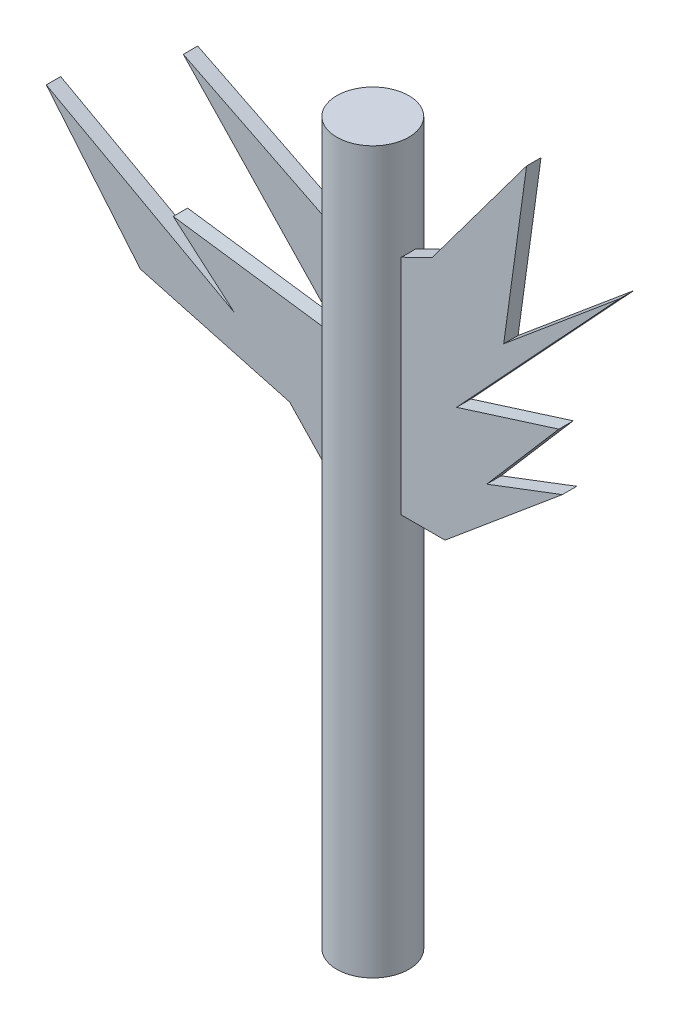
SolidWorks part; units mm, degrees
ref_plane "前视基准面" through (0, 0, 0) normal (0, 0, 1) x (1, 0, 0)
ref_plane "上视基准面" through (0, 0, 0) normal (0, 1, 0) x (1, 0, 0)
ref_plane "右视基准面" through (0, 0, 0) normal (1, 0, 0) x (0, 0, -1)
sketch "草图1" plane through (0, 0, 0) normal (0, 1, 0) x (1, 0, 0)
  circle A0 centre (0, 0) radius 25
  dimension "D1" = 50
extrude "凸台-拉伸1" add sketch "草图1" along normal blind 500
sketch "草图2" plane through (0, 0, 0) normal (0, 0, 1) x (1, 0, 0)
  line L0 (-4.9041, 415.8697) -> (-126.4768, 476.5639)
  line L1 (-126.4768, 476.5639) -> (-14.8453, 359.2715)
  line L2 (-14.8453, 359.2715) -> (-133.4749, 375.6967)
  line L3 (-133.4749, 375.6967) -> (-91.0534, 339.124)
  line L4 (-91.0534, 339.124) -> (-221.5366, 410.6732)
  line L5 (-221.5366, 410.6732) -> (-156.295, 332.6403)
  line L6 (-156.295, 332.6403) -> (-52.7298, 304.5742)
  line L7 (-52.7298, 304.5742) -> (-25, 275.4382)
  line L8 (-25, 500) -> (-25, 0) construction
  line L9 (-25, 275.4382) -> (55.0795, 275.4382)
  line L10 (55.0795, 275.4382) -> (136.5106, 343.521)
  line L11 (136.5106, 343.521) -> (84.0091, 323.5764)
  line L12 (84.0091, 323.5764) -> (134.0804, 381.6553)
  line L13 (134.0804, 381.6553) -> (63.0845, 359.2715)
  line L14 (63.0845, 359.2715) -> (176.0058, 480.8372)
  line L15 (176.0058, 480.8372) -> (95.795, 413.7748)
  line L16 (95.795, 413.7748) -> (111.6922, 528.5912)
  line L17 (111.6922, 528.5912) -> (46.0725, 440.6572)
  line L18 (46.0725, 440.6572) -> (-4.9041, 415.8697)
extrude "凸台-拉伸2" add sketch "草图2" along normal blind 5 and the other way blind 5
